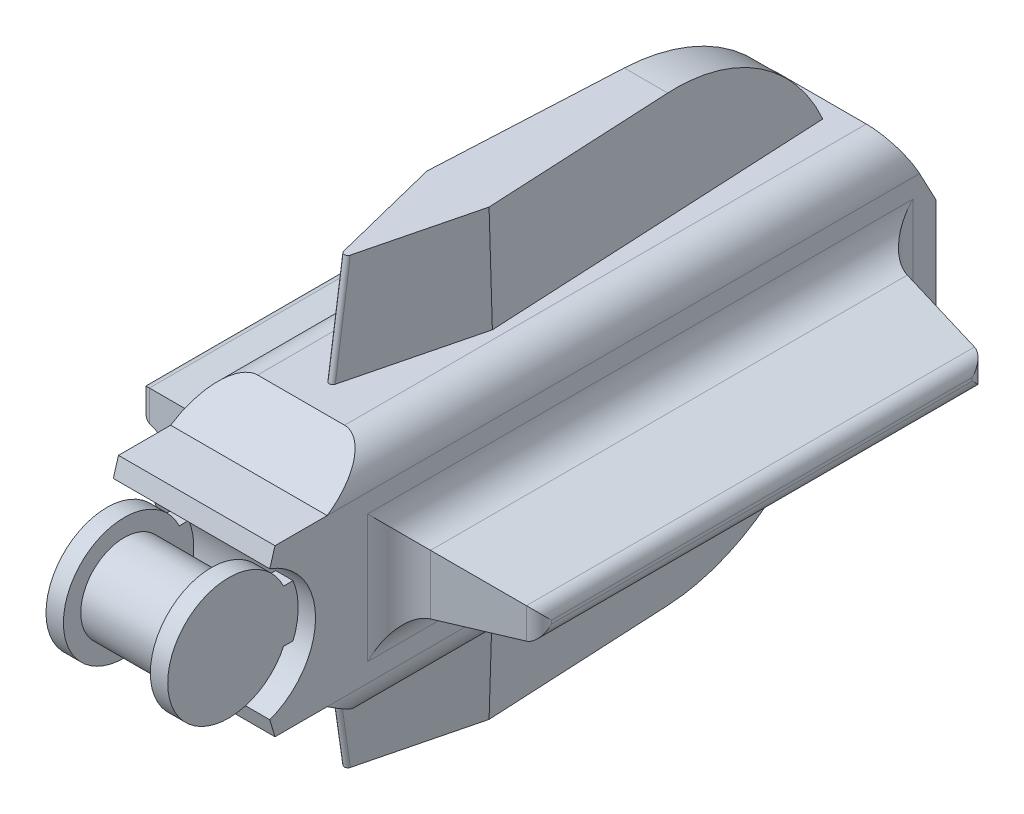
SolidWorks part; units mm, degrees
ref_plane "Front Plane" through (0, 0, 0) normal (0, 0, 1) x (1, 0, 0)
ref_plane "Top Plane" through (0, 0, 0) normal (0, 1, 0) x (1, 0, 0)
ref_plane "Right Plane" through (0, 0, 0) normal (1, 0, 0) x (0, 0, -1)
sketch "Sketch1" plane through (0, 0, 0) normal (1, 0, 0) x (0, 0, -1)
  circle A0 centre (0, 0) radius 3.175
  dimension "D1" = 6.35
extrude "Boss-Extrude1" add sketch "Sketch1" along normal mid plane 6.35
sketch "Sketch2" plane through (3.175, 0, 0) normal (1, 0, 0) x (0, 0, -1)
  circle A0 centre (0, 0) radius 4.445
  dimension "D1" = 8.89
extrude "Boss-Extrude2" add sketch "Sketch2" along normal blind 1.27
mirror "Mirror1" about plane through (0, 0, 0) normal (1, 0, 0) of "Boss-Extrude2"
sketch "Sketch3" plane through (4.445, 0, 0) normal (1, 0, 0) x (0, 0, -1)
  line L1 (0, 1.905) -> (6.35, 1.905)
  line L2 (0, 1.905) -> (0, -1.905)
  line L3 (0, -1.905) -> (6.35, -1.905)
  line L4 (6.35, 1.905) -> (6.35, -1.905)
  point P4 (0, 0)
  dimension "D1" = 3.81
  dimension "D2" = 6.35
extrude "Boss-Extrude3" add sketch "Sketch3" against normal blind 1.27
mirror "Mirror2" about plane through (0, 0, 0) normal (1, 0, 0) of "Boss-Extrude3"
sketch "Sketch4" plane through (-3.175, 0, 0) normal (1, 0, 0) x (0, 0, -1)
  line L0 (1.7375, 4.7736) -> (0, 0) construction
  line L1 (0, 0) -> (5.08, 0) construction
  line L2 (1.7375, 4.7736) -> (2.1185, 6.0436)
  line L3 (2.1185, 6.0436) -> (5.9285, 6.0436)
  line L4 (0, 0) -> (1.7375, -4.7736) construction
  line L5 (5.9285, 6.0436) -> (9.7385, 8.5836)
  line L6 (9.7385, 8.5836) -> (47.8385, 8.5836)
  line L7 (47.8385, 8.5836) -> (50.3785, 3.81)
  line L8 (50.3785, 3.81) -> (50.3785, -3.81)
  line L9 (50.3785, 0) -> (5.08, 0) construction
  line L10 (47.8385, -8.5836) -> (50.3785, -3.81)
  line L11 (9.7385, -8.5836) -> (47.8385, -8.5836)
  line L12 (5.9285, -6.0436) -> (9.7385, -8.5836)
  line L13 (2.1185, -6.0436) -> (5.9285, -6.0436)
  line L14 (1.7375, -4.7736) -> (2.1185, -6.0436)
  arc A0 (1.7375, 4.7736) -> (1.7375, -4.7736) centre (0, 0) cw
  dimension "D1" = 5.08
  dimension "D2" = 140
  dimension "D3" = 1.27
  dimension "D4" = 0.381
  dimension "D5" = 3.81
  dimension "D6" = 3.81
  dimension "D7" = 2.54
  dimension "D8" = 38.1
  dimension "D9" = 7.62
  dimension "D10" = 2.54
extrude "Boss-Extrude4" add sketch "Sketch4" against normal blind 2.54 and the other way blind 8.89
sketch "Sketch5" plane through (0, 0, -50.3785) normal (0, 0, -1) x (-1, 0, 0)
  circle A0 centre (0, 0) radius 3.175
  dimension "D1" = 6.35
extrude "Cut-Extrude1" cut sketch "Sketch5" against normal blind 12.7
fillet "Fillet1" radius 2.54 4 edges at (5.715, -8.5836, -28.7885) (-5.715, -8.5836, -28.7885) (-5.715, 8.5836, -28.7885) (5.715, 8.5836, -28.7885)
sketch "Sketch6" plane through (5.715, 0, 0) normal (1, 0, 0) x (0, 0, -1)
  line L0 (50.3785, -3.81) -> (50.3785, 3.81) construction
  line L1 (11.0085, 2.54) -> (46.5685, 2.54)
  line L2 (11.0085, 2.54) -> (11.0085, -2.54)
  line L3 (11.0085, -2.54) -> (46.5685, -2.54)
  line L4 (46.5685, 2.54) -> (46.5685, -2.54)
  point P4 (11.0085, 0)
  point P6 (50.3785, 0)
  dimension "D1" = 3.81
  dimension "D2" = 5.08
  dimension "D3" = 35.56
extrude "Boss-Extrude5" add sketch "Sketch6" along normal blind 8.89 draft 10
mirror "Mirror3" about plane through (0, 0, 0) normal (1, 0, 0) of "Boss-Extrude5"
fillet "Fillet2" radius 1.016 8 edges at (-14.605, -0.9725, -28.7885) (-14.605, 0, -45.0009) (-14.605, 0.9725, -28.7885) (-14.605, 0, -12.576) (14.605, 0.9725, -28.7885) (14.605, 0, -45.0009) (14.605, -0.9725, -28.7885) (14.605, 0, -12.576)
fillet "Fillet3" radius 2.54 8 edges at (5.715, -2.54, -28.7885) (5.715, 0, -11.0085) (5.715, 0, -46.5685) (5.715, 2.54, -28.7885) (-5.715, 0, -11.0085) (-5.715, 0, -46.5685) (-5.715, -2.54, -28.7885) (-5.715, 2.54, -28.7885)
sketch "Sketch7" plane through (0, 8.5836, 0) normal (0, 1, 0) x (1, 0, 0)
  line L0 (0, 9.7385) -> (0, 47.8385) construction
  line L1 (3.175, 9.7385) -> (-3.175, 9.7385) construction
  line L2 (3.175, 47.8385) -> (-3.175, 47.8385) construction
  line L3 (-1.27, 46.5685) -> (1.27, 46.5685)
  line L4 (1.27, 46.5685) -> (2.54, 21.1685)
  line L5 (2.54, 21.1685) -> (0, 11.0085)
  line L6 (0, 11.0085) -> (-2.54, 21.1685)
  line L7 (-2.54, 21.1685) -> (-1.27, 46.5685)
  point P8 (0, 46.5685)
  dimension "D1" = 2.54
  dimension "D2" = 1.27
  dimension "D3" = 1.27
  dimension "D4" = 2.54
  dimension "D5" = 25.4
extrude "Boss-Extrude6" add sketch "Sketch7" along normal blind 7.62 draft 2
mirror "Mirror4" about plane through (0, 0, 0) normal (0, 1, 0) of "Boss-Extrude6"
fillet "Fillet4" radius 0.254 2 edges at (0, -12.3936, -11.557) (0, 12.3936, -11.557)
fillet "Fillet5" radius 12.7 2 edges at (0, -16.2036, -46.3024) (0, 16.2036, -46.3024)
